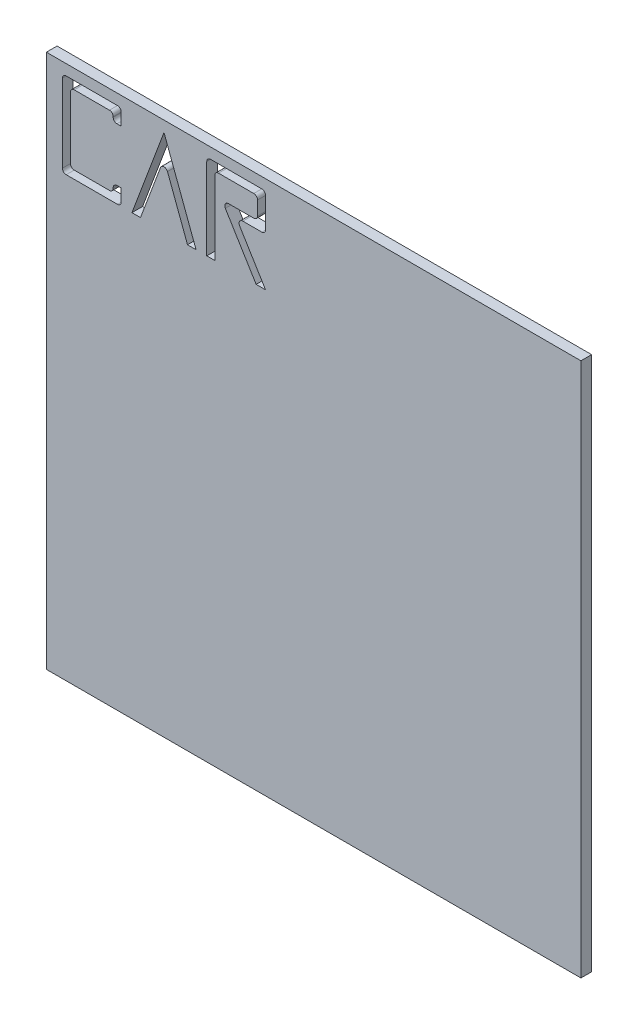
SolidWorks part; units mm, degrees
ref_plane "Plan de face" through (0, 0, 0) normal (0, 0, 1) x (1, 0, 0)
ref_plane "Plan de dessus" through (0, 0, 0) normal (0, 1, 0) x (1, 0, 0)
ref_plane "Plan de droite" through (0, 0, 0) normal (1, 0, 0) x (0, 0, -1)
sketch "Esquisse1" plane through (0, 0, 0) normal (0, 0, 1) x (1, 0, 0)
  line L1 (50, 50) -> (-50, 50)
  line L2 (50, 50) -> (50, -50)
  line L3 (50, -50) -> (-50, -50)
  line L4 (-50, 50) -> (-50, -50)
  line L5 (50, 50) -> (-50, -50) construction
  line L6 (50, -50) -> (-50, 50) construction
  point P0 (0, 0)
  dimension "D1" = 100
  dimension "D2" = 100
extrude "Boss.-Extru.1" add sketch "Esquisse1" along normal blind 2
sketch "Esquisse3" plane through (0, 0, 2) normal (0, 0, 1) x (1, 0, 0)
  line L0 (-36, 35) -> (-36, 32)
  line L1 (-36, 32) -> (-47, 32)
  line L2 (-47, 32) -> (-47, 48)
  line L3 (-47, 48) -> (-36, 48)
  line L4 (-36, 48) -> (-36, 45)
  line L5 (-34, 32) -> (-28, 48)
  line L6 (-28, 48) -> (-22, 32)
  line L7 (-20, 32) -> (-20, 48)
  line L8 (-20, 48) -> (-9, 48)
  line L9 (-9, 48) -> (-9, 41)
  line L10 (-9, 41) -> (-14.5, 41)
  line L11 (-14.5, 41) -> (-9, 32)
  line L12 (-6, 32) -> (-6, 48)
  line L13 (-6, 48) -> (4, 48)
  line L14 (4, 48) -> (4, 41)
  line L15 (4, 41) -> (-3, 41)
  line L16 (-3, 41) -> (4, 32)
  line L17 (7, 48) -> (7, 32)
  line L18 (7, 32) -> (17, 32)
  line L19 (17, 32) -> (17, 35)
  line L20 (7, 41) -> (16, 41)
  line L21 (7, 48) -> (17, 48)
  line L22 (17, 48) -> (17, 45)
  line L23 (23, 32) -> (23, 35)
  line L24 (23, 39) -> (23, 48)
  line L25 (23, 48) -> (33, 48)
  line L26 (33, 48) -> (33, 32)
  line L27 (33, 32) -> (23, 32)
  line L28 (23, 39) -> (30, 39)
  line L29 (36, 45) -> (36, 48)
  line L30 (36, 48) -> (46, 48)
  line L31 (46, 48) -> (46, 39)
  line L32 (46, 39) -> (36, 39)
  line L33 (36, 39) -> (36, 32)
  line L34 (-50, 32) -> (50, 32) construction
  line L35 (-50, 50) -> (-50, -50) construction
  line L36 (50, -50) -> (50, 50) construction
  line L37 (-50, 48) -> (50, 48) construction
  line L38 (-50, 35) -> (50, 35) construction
  line L39 (-50, 45) -> (50, 45) construction
  line L40 (-50, 41) -> (50, 41) construction
  line L41 (-50, 39) -> (50, 39) construction
  line L42 (36, 32) -> (46, 32)
  line L43 (46, 32) -> (46, 35)
  line L44 (-36, 45) -> (-36, 35) construction
  line L45 (-28, 48) -> (-28, 32) construction
  line L46 (-9, 41) -> (-9, 32) construction
  line L47 (4, 41) -> (4, 32) construction
  line L48 (17, 35) -> (17, 45) construction
  line L49 (23, 39) -> (23, 35) construction
  line L50 (36, 45) -> (36, 39) construction
  line L51 (46, 39) -> (46, 35) construction
  line L52 (-50, -50) -> (50, -50) construction
  line L53 (-37.5, 35) -> (-37.5, 33.5)
  line L54 (-37.5, 33.5) -> (-45.5, 33.5)
  line L55 (-45.5, 33.5) -> (-45.5, 46.5)
  line L56 (-45.5, 46.5) -> (-37.5, 46.5)
  line L57 (-37.5, 46.5) -> (-37.5, 45)
  line L58 (-37.5, 45) -> (-36, 45)
  line L59 (-37.5, 45) -> (-37.5, 35) construction
  line L60 (-37.5, 35) -> (-36, 35)
  line L61 (-32.398, 32) -> (-28, 43.728)
  line L62 (-28, 43.728) -> (-23.602, 32)
  line L63 (-34, 32) -> (-32.398, 32)
  line L64 (-22, 32) -> (-23.602, 32)
  line L65 (-20, 32) -> (-18.5, 32)
  line L66 (-28, 43.728) -> (-23.4045, 31.4733) construction
  line L67 (-32.5955, 31.4733) -> (-28, 43.728) construction
  line L68 (-18.5, 32) -> (-18.5, 46.5)
  line L69 (-18.5, 46.5) -> (-10.5, 46.5)
  line L70 (-10.5, 46.5) -> (-10.5, 42.5)
  line L71 (-10.5, 42.5) -> (-17.1746, 42.5)
  line L72 (-17.1746, 42.5) -> (-10.7579, 32)
  line L73 (-10.7579, 32) -> (-9, 32)
  point P25 (36, 46.5)
  dimension "D1" = 16
  dimension "D2" = 3
  dimension "D3" = 3
  dimension "D4" = 7
  dimension "D5" = 7
  dimension "D6" = 11
  dimension "D7" = 12
  dimension "D8" = 11
  dimension "D9" = 10
  dimension "D10" = 10
  dimension "D11" = 10
  dimension "D12" = 10
  dimension "D13" = 3
  dimension "D14" = 2
  dimension "D15" = 2
  dimension "D16" = 6
  dimension "D17" = 5.5
  dimension "D18" = 3
  dimension "D19" = 3
  dimension "D20" = 3
  dimension "D21" = 2
  dimension "D22" = 6
  dimension "D23" = 3
  dimension "D24" = 3
  dimension "D25" = 82
  dimension "D28" = 1.5
  dimension "D29" = 1.5
  dimension "D30" = 1.5
  dimension "D31" = 1.5
  dimension "D32" = 1.5
  dimension "D26" = 1.5
  dimension "D27" = 1.5
extrude "Enlèv. mat.-Extru.2" cut sketch "Esquisse3" against normal blind 10 contours L60 L53 L54 L55 L56 L57 L58 L4 L3 L2 L1 L0 | L64 L6 L5 L63 L61 L62 | L72 L73 L11 L10 L9 L8 L7 L65 L68 L69 L70 L71 region at (-36.1942, 33.5, 2) region at (-30.8127, 39.9298, 2) region at (-14.8665, 41.3311, 2)
fillet "Congé1" radius 0.7 19 edges at (-36, 48, 1) (-45.5, 46.5, 1) (-45.5, 33.5, 1) (-37.5, 33.5, 1) (-37.5, 45, 1) (-37.5, 35, 1) (-47, 48, 1) (-47, 32, 1) (-37.5, 46.5, 1) (-36, 32, 1) (-17.1746, 42.5, 1) (-9, 41, 1) (-9, 48, 1) (-10.5, 42.5, 1) (-20, 48, 1) (-10.5, 46.5, 1) (-18.5, 46.5, 1) (-14.5, 41, 1) (-28, 43.728, 1)
